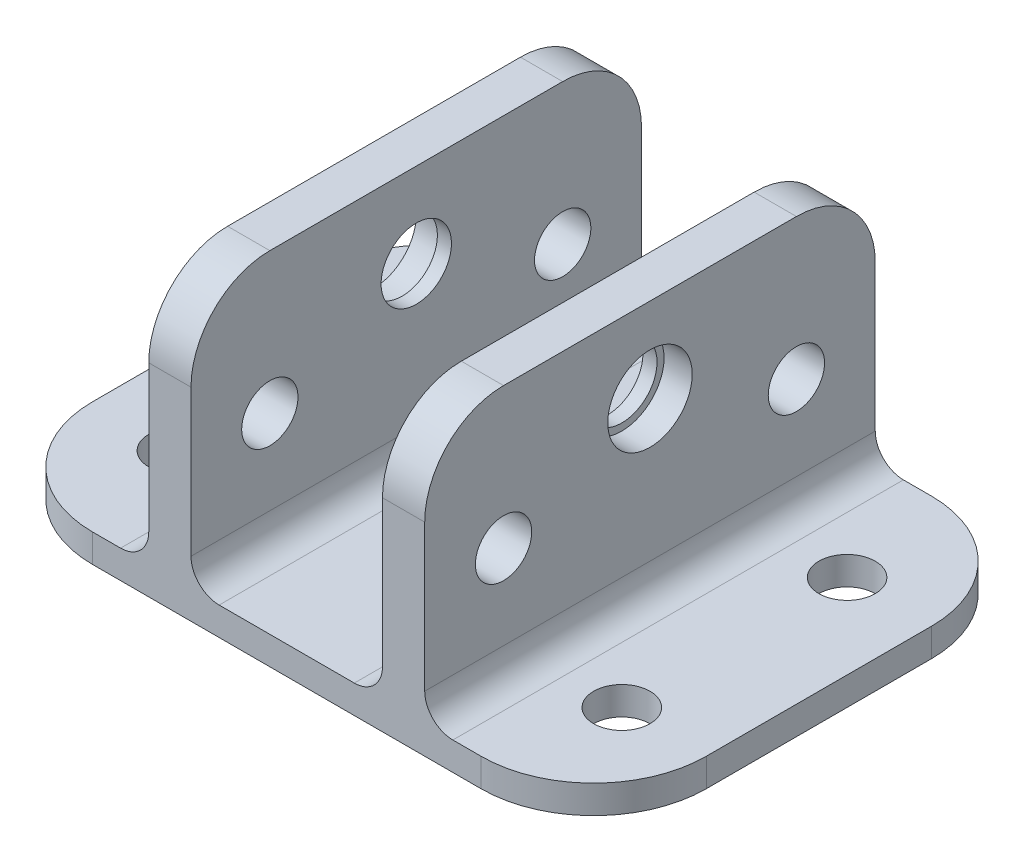
SolidWorks part; units mm, degrees
ref_plane "Front Plane" through (0, 0, 0) normal (0, 0, 1) x (1, 0, 0)
ref_plane "Top Plane" through (0, 0, 0) normal (0, 1, 0) x (1, 0, 0)
ref_plane "Right Plane" through (0, 0, 0) normal (1, 0, 0) x (0, 0, -1)
sketch "Sketch3" plane through (0, 0, 0) normal (0, 0, 1) x (1, 0, 0)
  line L0 (-34.6075, 0) -> (34.6075, 0)
  line L1 (34.6075, 0) -> (34.6075, 3.175)
  line L2 (34.6075, 3.175) -> (15.5575, 3.175)
  line L3 (15.5575, 3.175) -> (15.5575, 31.75)
  line L4 (15.5575, 31.75) -> (10.795, 31.75)
  line L5 (10.795, 31.75) -> (10.795, 3.175)
  line L6 (10.795, 3.175) -> (-10.795, 3.175)
  line L7 (-10.795, 3.175) -> (-10.795, 31.75)
  line L8 (-10.795, 31.75) -> (-15.5575, 31.75)
  line L9 (-15.5575, 31.75) -> (-15.5575, 3.175)
  line L10 (-15.5575, 3.175) -> (-34.6075, 3.175)
  line L11 (-34.6075, 3.175) -> (-34.6075, 0)
  point P15 (0, 0)
  dimension "D1" = 3.175
  dimension "D2" = 4.7625
  dimension "D3" = 28.575
  dimension "D4" = 19.05
  dimension "D5" = 21.59
extrude "Boss-Extrude2" add sketch "Sketch3" along normal blind 50.8
sketch "Sketch4" plane through (-15.5575, 0, 0) normal (-1, 0, 0) x (0, 0, 1)
  line L0 (25.4, 22.225) -> (0, 22.225) construction
  line L1 (8.89, 15.875) -> (0, 15.875) construction
  line L2 (41.91, 15.875) -> (50.8, 15.875) construction
  line L4 (0, 31.75) -> (0, 3.175)
  line L5 (0, 3.175) -> (50.8, 3.175)
  line L6 (50.8, 3.175) -> (50.8, 31.75)
  line L7 (50.8, 31.75) -> (0, 31.75)
  line L8 (0, 31.75) -> (0, 3.175)
  line L9 (0, 3.175) -> (50.8, 3.175)
  line L10 (50.8, 3.175) -> (50.8, 31.75)
  line L11 (50.8, 31.75) -> (0, 31.75)
  line L13 (25.4, 22.225) -> (50.8, 22.225) construction
  line L14 (8.89, 15.875) -> (8.89, 3.175) construction
  line L15 (41.91, 15.875) -> (41.91, 3.175) construction
  circle A0 centre (8.89, 15.875) radius 3.175
  circle A1 centre (41.91, 15.875) radius 3.175
  circle A2 centre (25.4, 22.225) radius 3.9688
  circle A3 centre (25.4, 22.225) radius 4.7625
  point P9 (25.4, 15.875)
  dimension "D2" = 6.35
  dimension "D3" = 9.525
  dimension "D4" = 7.9375
  dimension "D5" = 12.7
  dimension "D6" = 8.89
  dimension "D7" = 19.05
  dimension "D1" = 0
extrude "Cut-Extrude1" cut sketch "Sketch4" against normal through all contours A0 | A1 | A2 region at (-15.5575, 15.875, 8.89) region at (-15.5575, 15.875, 41.91) region at (-15.5575, 22.225, 25.4)
sketch "Sketch5" plane through (0, 3.175, 0) normal (0, 1, 0) x (1, 0, 0)
  line L0 (34.6075, 0) -> (15.5575, 0) construction
  line L1 (15.5575, 0) -> (15.5575, -50.8) construction
  line L2 (15.5575, -50.8) -> (34.6075, -50.8) construction
  line L3 (34.6075, -50.8) -> (34.6075, 0) construction
  line L4 (15.5575, 0) -> (10.795, 0) construction
  line L5 (10.795, 0) -> (10.795, -50.8) construction
  line L6 (10.795, -50.8) -> (15.5575, -50.8) construction
  line L7 (15.5575, -50.8) -> (15.5575, 0) construction
  line L8 (10.795, 0) -> (-10.795, 0) construction
  line L9 (-10.795, 0) -> (-10.795, -50.8) construction
  line L10 (-10.795, -50.8) -> (10.795, -50.8) construction
  line L11 (10.795, -50.8) -> (10.795, 0) construction
  line L12 (-10.795, 0) -> (-15.5575, 0) construction
  line L13 (-15.5575, 0) -> (-15.5575, -50.8) construction
  line L14 (-15.5575, -50.8) -> (-10.795, -50.8) construction
  line L15 (-10.795, -50.8) -> (-10.795, 0) construction
  line L16 (-15.5575, 0) -> (-34.6075, 0) construction
  line L17 (-34.6075, 0) -> (-34.6075, -50.8) construction
  line L18 (-34.6075, -50.8) -> (-15.5575, -50.8) construction
  line L19 (-15.5575, -50.8) -> (-15.5575, 0) construction
  line L20 (34.6075, 0) -> (15.5575, 0)
  line L21 (15.5575, 0) -> (15.5575, -50.8)
  line L22 (15.5575, -50.8) -> (34.6075, -50.8)
  line L23 (34.6075, -50.8) -> (34.6075, 0)
  line L24 (15.5575, 0) -> (10.795, 0)
  line L25 (10.795, 0) -> (10.795, -50.8)
  line L26 (10.795, -50.8) -> (15.5575, -50.8)
  line L27 (15.5575, -50.8) -> (15.5575, 0)
  line L28 (10.795, 0) -> (-10.795, 0)
  line L29 (-10.795, 0) -> (-10.795, -50.8)
  line L30 (-10.795, -50.8) -> (10.795, -50.8)
  line L31 (10.795, -50.8) -> (10.795, 0)
  line L32 (-10.795, 0) -> (-15.5575, 0)
  line L33 (-15.5575, 0) -> (-15.5575, -50.8)
  line L34 (-15.5575, -50.8) -> (-10.795, -50.8)
  line L35 (-10.795, -50.8) -> (-10.795, 0)
  line L36 (-15.5575, 0) -> (-34.6075, 0)
  line L37 (-34.6075, 0) -> (-34.6075, -50.8)
  line L38 (-34.6075, -50.8) -> (-15.5575, -50.8)
  line L39 (-15.5575, -50.8) -> (-15.5575, 0)
  line L40 (-25.0825, 0) -> (-25.0825, -12.7) construction
  line L41 (25.0825, 0) -> (25.0825, -12.7) construction
  line L42 (-34.6075, -25.4) -> (34.6075, -25.4) construction
  line L43 (-25.0825, -50.8) -> (-25.0825, -38.1) construction
  line L44 (-25.0825, -12.7) -> (-25.0825, -25.4) construction
  line L45 (-25.0825, -25.4) -> (-25.0825, -38.1) construction
  line L46 (-25.0825, -38.1) -> (-25.0825, -50.8) construction
  line L47 (-25.0825, -12.7) -> (-25.0825, 0) construction
  line L48 (25.0825, -50.8) -> (25.0825, -38.1) construction
  line L49 (25.0825, -12.7) -> (25.0825, -25.4) construction
  line L50 (25.0825, -25.4) -> (25.0825, -38.1) construction
  line L51 (0, 0) -> (0, -50.8) construction
  circle A0 centre (-25.0825, -12.7) radius 3.175
  circle A1 centre (-25.0825, -38.1) radius 3.175
  circle A2 centre (25.0825, -12.7) radius 3.175
  circle A3 centre (25.0825, -38.1) radius 3.175
  point P26 (9.525, -25.4)
  point P31 (9.525, -25.4)
  point P34 (-25.0825, -25.4)
  point P36 (-25.0825, -25.4)
  point P39 (9.525, -25.4)
  dimension "D1" = 6.35
  dimension "D2" = 12.7
extrude "Cut-Extrude2" cut sketch "Sketch5" against normal through all contours A1 | A0 | A2 | A3 region at (-25.0825, 3.175, 12.7) region at (-25.0825, 3.175, 38.1) region at (25.0825, 3.175, 12.7) region at (25.0825, 3.175, 38.1)
extrude "Cut-Extrude3" cut sketch "Sketch4<3>" against normal blind 3.175 contours A3 A2 region at (-15.5575, 22.225, 20.7722)
sketch "Sketch4<3>" plane through (-15.5575, 0, 0) normal (-1, 0, 0) x (0, 0, 1) same geometry as "Sketch4"
sketch "Sketch6" plane through (15.5575, 0, 0) normal (1, 0, 0) x (0, 0, -1)
  line L4 (0, 3.175) -> (0, 31.75)
  line L5 (0, 31.75) -> (-50.8, 31.75)
  line L6 (-50.8, 31.75) -> (-50.8, 3.175)
  line L7 (-50.8, 3.175) -> (0, 3.175)
  line L8 (0, 3.175) -> (0, 31.75)
  line L9 (0, 31.75) -> (-50.8, 31.75)
  line L10 (-50.8, 31.75) -> (-50.8, 3.175)
  line L11 (-50.8, 3.175) -> (0, 3.175)
  circle A0 centre (-25.4, 22.225) radius 4.7625
  circle A1 centre (-25.4, 22.225) radius 3.9688 construction
  circle A2 centre (-25.4, 22.225) radius 3.9688
  circle M8 centre (-25.4, 22.225) radius 3.9688
  dimension "D2" = 9.525
  dimension "D1" = 0
extrude "Cut-Extrude4" cut sketch "Sketch6" against normal blind 3.175 contours A0 M8 region at (15.5575, 22.225, 30.0278)
fillet "Fillet1" radius 12.7 4 edges at (34.6075, 1.5875, 0) (34.6075, 1.5875, 50.8) (-34.6075, 1.5875, 50.8) (-34.6075, 1.5875, 0)
fillet "Fillet2" radius 3.175 4 edges at (15.5575, 3.175, 25.4) (10.795, 3.175, 25.4) (-10.795, 3.175, 25.4) (-15.5575, 3.175, 25.4)
fillet "Fillet3" radius 8.89 4 edges at (-13.1762, 31.75, 50.8) (13.1762, 31.75, 50.8) (13.1762, 31.75, 0) (-13.1762, 31.75, 0)
